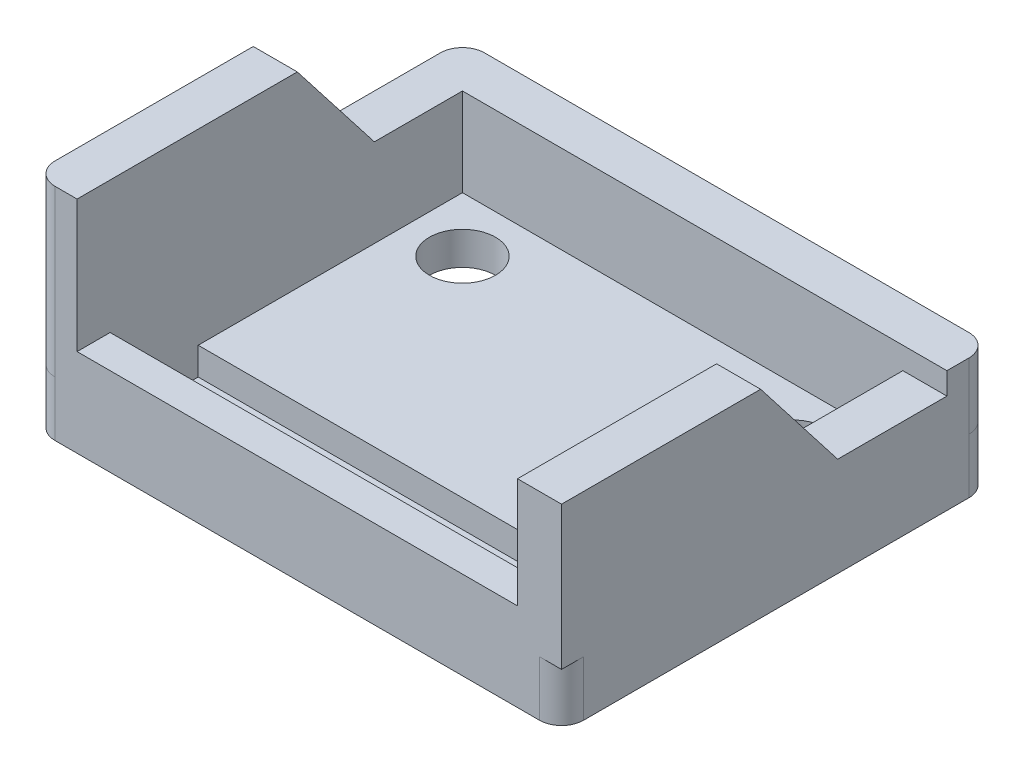
SolidWorks part; units mm, degrees
ref_plane "Front Plane" through (0, 0, 0) normal (0, 0, 1) x (1, 0, 0)
ref_plane "Top Plane" through (0, 0, 0) normal (0, 1, 0) x (1, 0, 0)
ref_plane "Right Plane" through (0, 0, 0) normal (1, 0, 0) x (0, 0, -1)
sketch "Sketch3" plane through (0, 0, 0) normal (0, 1, 0) x (1, 0, 0)
  line L0 (12, 17.5) -> (12, 1.5) construction
  line L1 (1, 0) -> (23, 0)
  line L2 (0, 1) -> (0, 18.5)
  line L3 (1, 19.5) -> (23, 19.5)
  line L4 (24, 1) -> (24, 18.5)
  line L5 (2, 1.5) -> (22, 1.5)
  line L6 (2, 1.5) -> (2, 17.5)
  line L7 (2, 17.5) -> (22, 17.5)
  line L8 (22, 1.5) -> (22, 17.5)
  line L9 (2, 1.5) -> (2, 0)
  line L10 (22, 1.5) -> (22, 0)
  line L11 (2, 5.5) -> (22, 5.5)
  circle A2 centre (4.5, 15) radius 1.5
  circle A3 centre (19.5, 15) radius 1.5
  arc A4 (23, 19.5) -> (24, 18.5) centre (23, 18.5) cw
  arc A5 (23, 0) -> (24, 1) centre (23, 1) ccw
  arc A6 (1, 0) -> (0, 1) centre (1, 1) cw
  arc A7 (0, 18.5) -> (1, 19.5) centre (1, 18.5) cw
  point P23 (24, 0)
  point P26 (0, 0)
  point P29 (0, 19.5)
  dimension "D3" = 2
  dimension "D4" = 1.5
  dimension "D5" = 2
  dimension "D7" = 3
  dimension "D8" = 2.5
  dimension "D9" = 2.5
  dimension "D12" = 1
  dimension "D1" = 24
  dimension "D2" = 19.5
  dimension "D6" = 2
  dimension "D10" = 2
  dimension "D11" = 2
  dimension "D13" = 4
extrude "Boss-Extrude2" add sketch "Sketch3" along normal blind 1.5 contours L0 L7 L6 L11 A2 | L7 L0 L11 L8 A3 region at (16.8435, 0, -11.2809) region at (7.1565, 0, -11.2809)
extrude "Boss-Extrude4" add sketch "Sketch3<5>" along normal blind 4 contours L10 L5 L9 L1 region at (12, 0, -0.75)
sketch "Sketch3<5>" plane through (0, 0, 0) normal (0, 1, 0) x (1, 0, 0) same geometry as "Sketch3"
extrude "Boss-Extrude5" add sketch "Sketch3<6>" along normal blind 0.25 contours L11 L0 L5 L8 | L0 L11 L6 L5 region at (17, 0, -3.5) region at (7, 0, -3.5)
sketch "Sketch3<6>" plane through (0, 0, 0) normal (0, 1, 0) x (1, 0, 0) same geometry as "Sketch3"
extrude "Boss-Extrude7" add sketch "Sketch3<8>" along normal blind 2.5 contours A7 L2 A6 L1 L9 L6 L7 L8 L10 A5 L4 A4 L3 region at (0.5116, 0, -0.5116)
sketch "Sketch3<8>" plane through (0, 0, 0) normal (0, 1, 0) x (1, 0, 0) same geometry as "Sketch3"
sketch "Sketch4" plane through (24, 0, 0) normal (1, 0, 0) x (0, 0, -1)
  line L0 (19.5, 2.5) -> (19.5, 5.5)
  line L1 (19.5, 5.5) -> (13.5, 5.5)
  line L2 (13.5, 5.5) -> (10, 10)
  line L3 (10, 10) -> (0, 10)
  line L4 (0, 10) -> (0, 2.5)
  line L5 (0, 2.5) -> (19.5, 2.5)
  line L7 (17.5, 5.5) -> (17.5, 2.5)
  line L8 (0, 9) -> (9.0407, 9)
  line L9 (9.0407, 9) -> (12.54, 4.5)
  line L10 (12.54, 4.5) -> (17.5, 4.5)
  point P15 (0, 0)
  point P16 (0, 0)
  line M3 (18.5, 2.5) -> (1, 2.5)
  dimension "D1" = 7.5
  dimension "D2" = 3
  dimension "D3" = 2
  dimension "D4" = 6
  dimension "D5" = 10
  dimension "D6" = 1
  dimension "D7" = 1
  dimension "D8" = 127.875
  dimension "D9" = 127.87
sketch "Sketch9" plane through (0, 0, 0) normal (1, 0, 0) x (0, 0, -1)
  line L0 (19.5, 2.5) -> (19.5, 5.5)
  line L1 (19.5, 5.5) -> (13.5, 5.5)
  line L2 (13.5, 5.5) -> (10, 10)
  line L3 (10, 10) -> (0, 10)
  line L4 (0, 10) -> (0, 2.5)
  line L5 (0, 2.5) -> (19.5, 2.5)
  line L7 (17.5, 5.5) -> (17.5, 2.5)
  dimension "D1" = 7.5
  dimension "D2" = 3
  dimension "D3" = 2
  dimension "D4" = 6
  dimension "D5" = 10
extrude "Boss-Extrude10" add sketch "Sketch9" along normal up to surface (2 mm away) contours L7 L1 L2 L3 L4 L5 region at (0, 5.8256, -7.3292) up to face at (2, 3.25, -0.75)
extrude "Boss-Extrude11" add sketch "Sketch4" against normal through all contours L1 L7 L5 L0 M3 region at (24, 4, -18.5)
fillet "Fillet5" radius 1 2 edges at (24, 4, -19.5) (0, 4, -19.5)
fillet "Fillet6" radius 1 1 edges at (0, 6.25, 0)
extrude "Boss-Extrude12" add sketch "Sketch4<4>" against normal up to surface (2 mm away) contours L10 L9 L8 L4 L5 L7 region at (24, 5.318, -6.8279) up to face at (22, 3.25, -0.75)
sketch "Sketch4<4>" plane through (24, 0, 0) normal (1, 0, 0) x (0, 0, -1) same geometry as "Sketch4"
